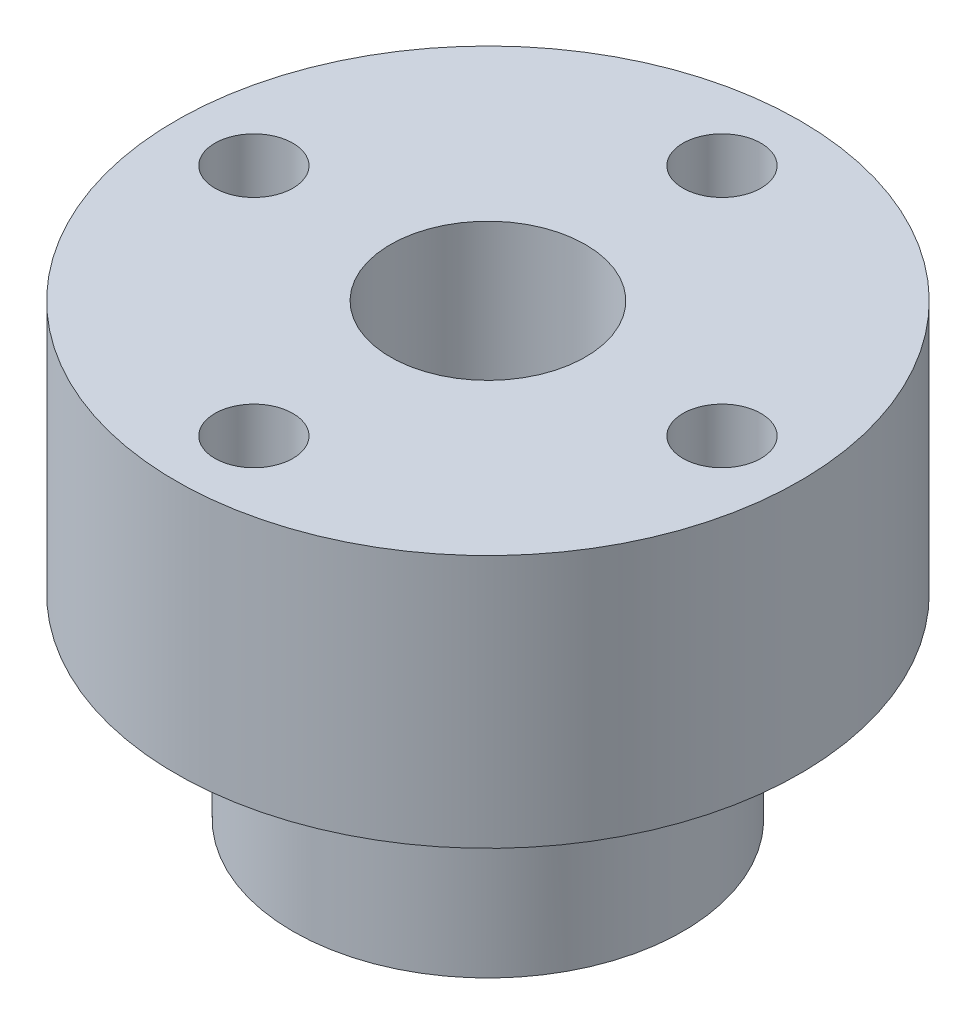
SolidWorks part; units mm, degrees
ref_plane "前视基准面" through (0, 0, 0) normal (0, 0, 1) x (1, 0, 0)
ref_plane "上视基准面" through (0, 0, 0) normal (0, 1, 0) x (1, 0, 0)
ref_plane "右视基准面" through (0, 0, 0) normal (1, 0, 0) x (0, 0, -1)
sketch "草图1" plane through (0, 0, 0) normal (0, 1, 0) x (1, 0, 0)
  circle A0 centre (0, 0) radius 16
  circle A1 centre (0, 12) radius 2
  circle A2 centre (12, 0) radius 2
  circle A3 centre (0, -12) radius 2
  circle A4 centre (-12, 0) radius 2
  circle A5 centre (0, 0) radius 5
  circle A6 centre (0, 0) radius 10
  point P14 (0, 0)
  dimension "D1" = 32
  dimension "D2" = 4
  dimension "D5" = 10
  dimension "D6" = 20
  dimension "D3" = 12
  dimension "D4" = 4
extrude "凸台-拉伸1" add sketch "草图1" along normal blind 13 contours A0 A6 A3 A4 A1 A2 | A6 A5 region at (-15.5475, 0, 0) region at (6.8711, 0, -6.8711)
extrude "凸台-拉伸2" add sketch "草图1<3>" against normal blind 10 contours A6 A5 region at (6.8711, 0, -6.8711)
sketch "草图1<3>" plane through (0, 0, 0) normal (0, 1, 0) x (1, 0, 0) same geometry as "草图1"
